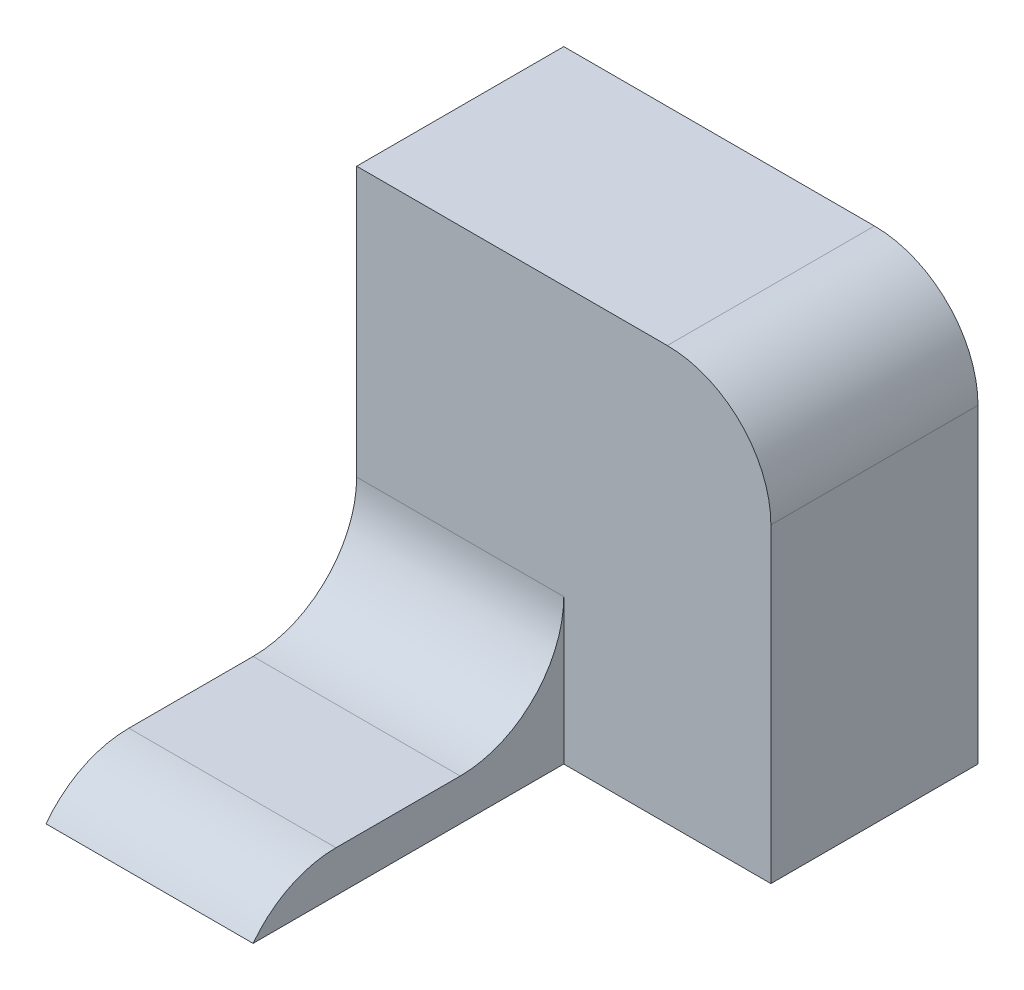
SolidWorks part; units mm, degrees
ref_plane "Front Plane" through (0, 0, 0) normal (0, 0, 1) x (1, 0, 0)
ref_plane "Top Plane" through (0, 0, 0) normal (0, 1, 0) x (1, 0, 0)
ref_plane "Right Plane" through (0, 0, 0) normal (1, 0, 0) x (0, 0, -1)
sketch "Sketch1" plane through (0, 0, 0) normal (0, 0, 1) x (1, 0, 0)
  line L1 (-30, -4) -> (-10, -4)
  line L2 (-10, -4) -> (-10, 0)
  line L3 (-10, 0) -> (-30, 0)
  line L4 (-30, 0) -> (-30, -4)
  dimension "D1" = 20
  dimension "Width" = 4
extrude "Boss-Extrude1" add sketch "Sketch1" along normal blind 30
sketch "Sketch2" plane through (0, 0, 0) normal (0, 0, 1) x (1, 0, 0)
  line L1 (-30, -4) -> (10, -4)
  line L2 (10, -4) -> (10, 36)
  line L3 (10, 36) -> (-30, 36)
  line L4 (-30, 36) -> (-30, -4)
  dimension "D1" = 40
  dimension "Width" = 40
extrude "Boss-Extrude2" add sketch "Sketch2" against normal blind 20
fillet "Fillet1" radius 10 3 edges at (-20, 0, 0) (10, 36, -10) (-20, 0, 30)
